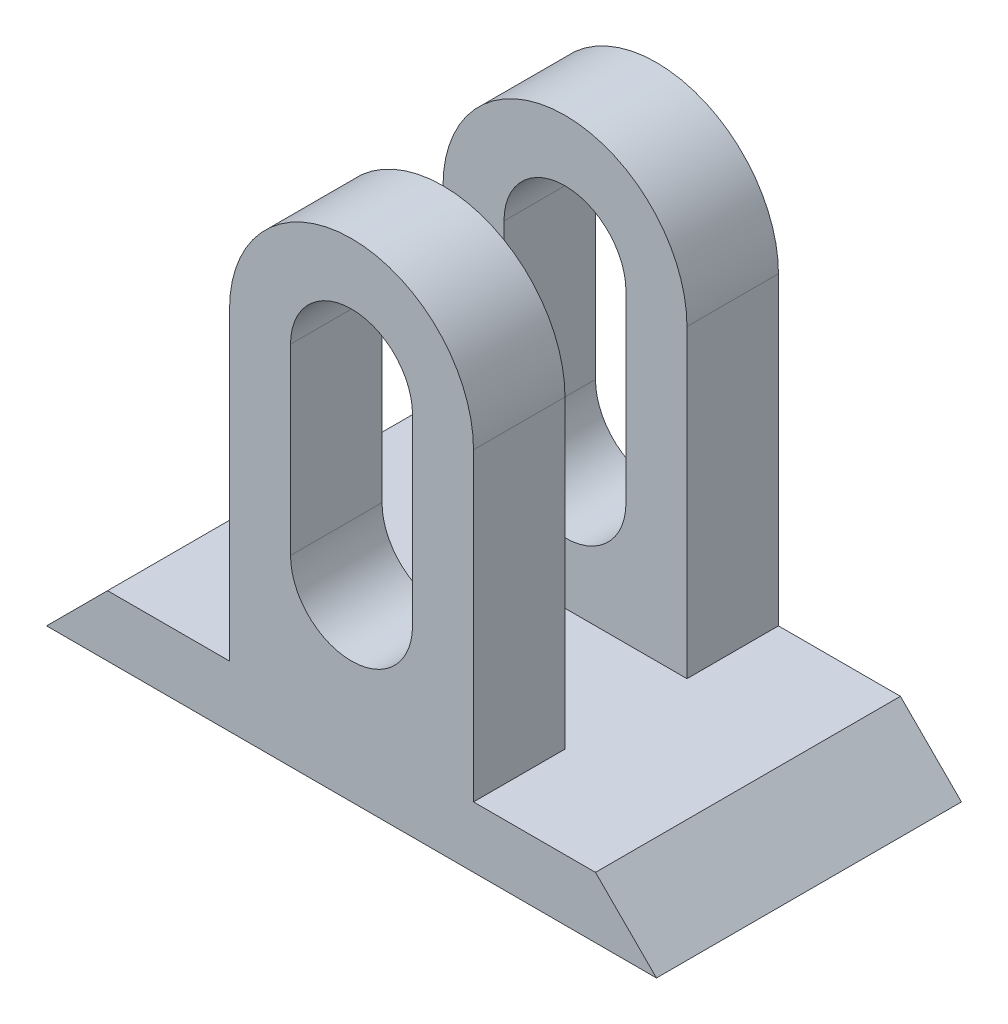
SolidWorks part; units mm, degrees
ref_plane "Front Plane" through (0, 0, 0) normal (0, 0, 1) x (1, 0, 0)
ref_plane "Top Plane" through (0, 0, 0) normal (0, 1, 0) x (1, 0, 0)
ref_plane "Right Plane" through (0, 0, 0) normal (1, 0, 0) x (0, 0, -1)
sketch "Sketch1" plane through (0, 0, 0) normal (0, 0, 1) x (1, 0, 0)
  line L0 (0, 0) -> (100, 0)
  line L1 (100, 0) -> (90, 10)
  line L2 (90, 10) -> (70, 10)
  line L3 (70, 10) -> (70, 60)
  line L4 (30, 60) -> (30, 10)
  line L5 (30, 10) -> (10, 10)
  line L6 (10, 10) -> (0, 0)
  line L7 (50, 60) -> (50, 30) construction
  line L8 (60, 60) -> (60, 30)
  line L9 (40, 60) -> (40, 30)
  line L10 (30, 10) -> (70, 10)
  arc A0 (70, 60) -> (30, 60) centre (50, 60) ccw
  arc A1 (60, 60) -> (40, 60) centre (50, 60) ccw
  arc A2 (40, 30) -> (60, 30) centre (50, 30) ccw
  point P8 (50, 45)
  dimension "D1" = 100
  dimension "D6" = 20
  dimension "D7" = 10
  dimension "D2" = 10
  dimension "D3" = 10
  dimension "D4" = 10
  dimension "D5" = 30
  dimension "D8" = 30
  dimension "D9" = 60
extrude "Boss-Extrude1" add sketch "Sketch1" along normal blind 50 contours L10 L5 L6 L0 L1 L2 region at (50, 4.8148, 0)
extrude "Boss-Extrude2" add sketch "Sketch1<3>" along normal blind 15 contours L3 A0 L4 L10 A2 L9 A1 L8 region at (30.8062, 35, 0)
sketch "Sketch1<3>" plane through (0, 0, 0) normal (0, 0, 1) x (1, 0, 0) same geometry as "Sketch1"
extrude "Boss-Extrude3" add sketch "Sketch1<4>" against normal blind 15 from surface contours L3 A0 L4 L10 A2 L9 A1 L8 region at (30.8062, 35, 0) starting at face at (50, 5, 50)
sketch "Sketch1<4>" plane through (0, 0, 0) normal (0, 0, 1) x (1, 0, 0) same geometry as "Sketch1"
